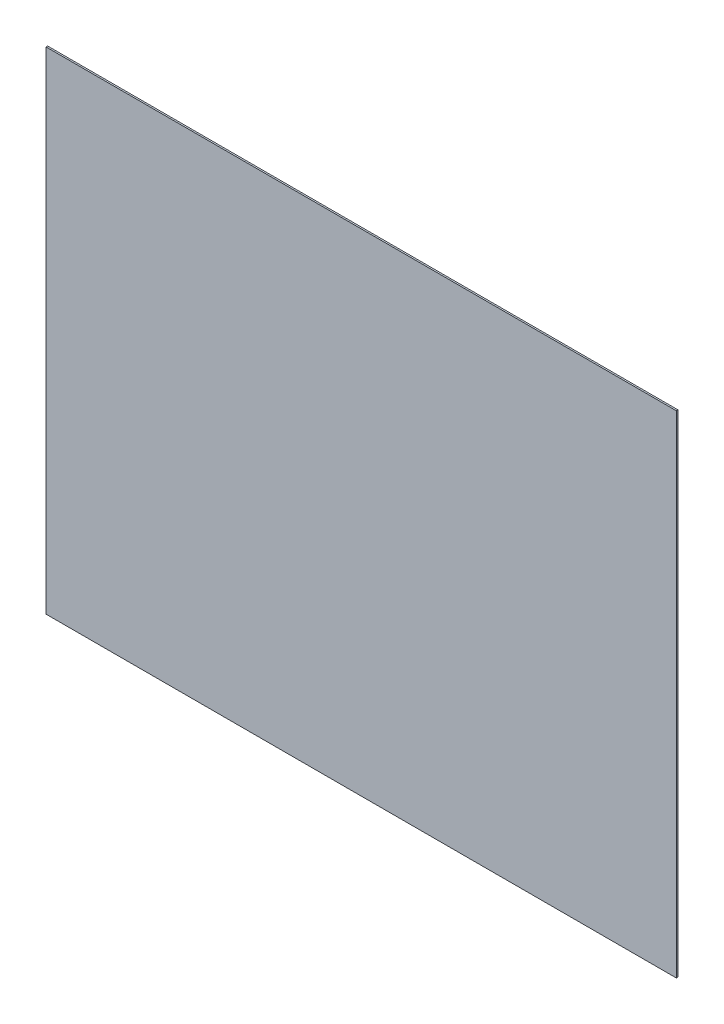
SolidWorks part; units mm, degrees
material "ABS"
ref_plane "X-Y Datum" through (0, 0, 0) normal (0, 0, 1) x (1, 0, 0)
ref_plane "X-Z Datum" through (0, 0, 0) normal (0, 1, 0) x (1, 0, 0)
ref_plane "Y-Z Datum" through (0, 0, 0) normal (1, 0, 0) x (0, 0, -1)
sketch "Sketch2" plane through (0, 0, 0) normal (0, 0, 1) x (1, 0, 0)
  line L4 (-157.564, 102.4228) -> (-157.5131, -381.8282)
  line L5 (-157.5131, -381.8282) -> (463.7455, -381.7629)
  line L6 (463.7455, -381.7629) -> (463.6946, 102.4881)
  line L7 (463.6946, 102.4881) -> (-157.564, 102.4228)
  line L8 (-157.564, 102.4228) -> (-157.5131, -381.8282)
  line L9 (-157.5131, -381.8282) -> (463.7455, -381.7629)
  line L10 (463.7455, -381.7629) -> (463.6946, 102.4881)
  line L11 (463.6946, 102.4881) -> (-157.564, 102.4228)
  dimension "D1" = 0
extrude "Boss-Extrude1" add sketch "Sketch2" along normal blind 1.5875
